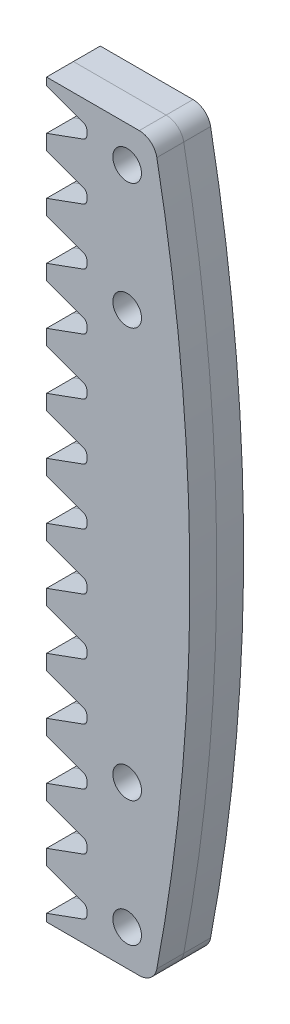
SolidWorks part; units mm, degrees
material "碳纤维"
ref_plane "前视基准面" through (0, 0, 0) normal (0, 0, 1) x (1, 0, 0)
ref_plane "上视基准面" through (0, 0, 0) normal (0, 1, 0) x (1, 0, 0)
ref_plane "右视基准面" through (0, 0, 0) normal (1, 0, 0) x (0, 0, -1)
ref_axis "基准轴1" through (0, -55, 0) along (0, 1, 0)
sketch "SketchCI.m_strSketchName" plane through (0, 0, 0) normal (0, 0, 1) x (1, 0, 0)
  line L0 (-2, 3.1416) -> (-2, -78.5398)
  line L1 (-2, -78.5398) -> (10, -78.5398)
  line L2 (10, -78.5398) -> (10, 3.1416)
  line L3 (10, 3.1416) -> (-2, 3.1416)
  dimension "D1" = 10
  dimension "D2" = 2
  dimension "D3" = 3.1416
  dimension "D4" = 81.6814
extrude "拉伸CI" add sketch "SketchCI.m_strSketchName" along normal mid plane 3
sketch "齿草图大直齿轮" plane through (0, 0, 0) normal (0, 0, 1) x (1, 0, 0)
  line L0 (-2.8229, 2.5983) -> (-2.8229, -2.5983)
  line L1 (-2.8229, -2.5983) -> (2.1052, -0.8046)
  line L2 (2.5, -0.2407) -> (2.5, 0.2407)
  line L3 (2.1052, 0.8046) -> (-2.8229, 2.5983)
  arc A0 (2.1052, -0.8046) -> (2.5, -0.2407) centre (1.9, -0.2407) ccw
  arc A1 (2.5, 0.2407) -> (2.1052, 0.8046) centre (1.9, 0.2407) ccw
  dimension "D1" = 1.2
  dimension "D2" = 1.2
  dimension "FLANKONEANGLE" = 70
  dimension "FLANKTWOANGLE" = 70
extrude "齿拉伸切除大直齿轮" cut sketch "齿草图大直齿轮" against normal through all both and the other way through all
pattern_linear "齿形大直齿轮" count 13 spacing 6.2832 along (0, -1, 0) of "齿拉伸切除大直齿轮"
sketch "辅助草图大直齿轮" plane through (0, 0, 0) normal (0, 0, 1) x (1, 0, 0)
  line L0 (0, 0) -> (0, -81.6814) construction
sketch "草图2" plane through (0, 0, 1.5) normal (0, 0, 1) x (1, 0, 0)
  line L0 (-2, -78.5398) -> (10, -78.5398) construction
  line L1 (10, 3.1416) -> (-2, 3.1416)
  line L2 (10, 3.1416) -> (10, -78.5398)
  line L3 (10, -78.5398) -> (-2, -78.5398)
  line L4 (-2, 3.1416) -> (-2, -78.5398)
  dimension "D1" = 12
sketch "草图7" plane through (0, 0, -1.5) normal (0, 0, -1) x (-1, 0, 0)
  line L1 (-2.5, -37.6991) -> (-10, -37.6991) construction
  line L3 (-2.5, -37.9399) -> (-2.5, -37.4584) construction
  line L5 (-7, -14.8584) -> (-7, -0.8584) construction
  line L6 (-10, -78.5398) -> (-10, 3.1416) construction
  line L7 (-10, 3.1416) -> (2, 3.1416) construction
  circle A1 centre (-7, -14.8584) radius 1.6
  circle A2 centre (-7, -0.8584) radius 1.6
  circle A5 centre (-7, -74.5398) radius 1.6
  circle A6 centre (-7, -60.5398) radius 1.6
  dimension "D1" = 3.2
  dimension "D2" = 4
  dimension "D3" = 3
  dimension "D4" = 14
extrude "切除-拉伸3" cut sketch "草图7" against normal through all
sketch "草图8" plane through (0, 0, -1.5) normal (0, 0, -1) x (-1, 0, 0)
  line L0 (-10, -37.6991) -> (196.4954, -37.6991) construction
  line L1 (-10, -78.5398) -> (-10, 3.1416) construction
  line L2 (-10, -37.6991) -> (-14, -37.6991) construction
  line L3 (-10, -78.5398) -> (-10, 3.1416)
  arc A0 (-10, 3.1416) -> (-10, -78.5398) centre (196.4954, -37.6991) ccw
  dimension "D1" = 4
extrude "凸台-拉伸1" add sketch "草图8" against normal up to surface (3 mm away) up to face at (5.4, -0.8584, 1.5)
fillet "圆角1" radius 2 2 edges at (10, 3.1416, 0) (10, -78.5398, 0)
sketch "草图9" plane through (0, 0, 1.5) normal (0, 0, 1) x (1, 0, 0)
  line L55 (8.3502, 3.1416) -> (-2, 3.1416)
  line L56 (-2, 3.1416) -> (-2, 2.2987)
  line L57 (-2, 2.2987) -> (2.1052, 0.8046)
  line L58 (2.5, 0.2407) -> (2.5, -0.2407)
  line L59 (2.1052, -0.8046) -> (-2, -2.2987)
  line L60 (-2, -2.2987) -> (-2, -3.9844)
  line L61 (-2, -3.9844) -> (2.1052, -5.4786)
  line L62 (2.5, -6.0424) -> (2.5, -6.5239)
  line L63 (2.1052, -7.0877) -> (-2, -8.5819)
  line L64 (-2, -8.5819) -> (-2, -10.2676)
  line L65 (-2, -10.2676) -> (2.1052, -11.7618)
  line L66 (2.5, -12.3256) -> (2.5, -12.8071)
  line L67 (2.1052, -13.3709) -> (-2, -14.8651)
  line L68 (-2, -14.8651) -> (-2, -16.5508)
  line L69 (-2, -16.5508) -> (2.1052, -18.045)
  line L70 (2.5, -18.6088) -> (2.5, -19.0903)
  line L71 (2.1052, -19.6541) -> (-2, -21.1483)
  line L72 (-2, -21.1483) -> (-2, -22.834)
  line L73 (-2, -22.834) -> (2.1052, -24.3282)
  line L74 (2.5, -24.892) -> (2.5, -25.3735)
  line L75 (2.1052, -25.9373) -> (-2, -27.4315)
  line L76 (-2, -27.4315) -> (-2, -29.1172)
  line L77 (-2, -29.1172) -> (2.1052, -30.6114)
  line L78 (2.5, -31.1752) -> (2.5, -31.6567)
  line L79 (2.1052, -32.2205) -> (-2, -33.7147)
  line L80 (-2, -33.7147) -> (-2, -35.4004)
  line L81 (-2, -35.4004) -> (2.1052, -36.8946)
  line L82 (2.5, -37.4584) -> (2.5, -37.9399)
  line L83 (2.1052, -38.5037) -> (-2, -39.9978)
  line L84 (-2, -39.9978) -> (-2, -41.6836)
  line L85 (-2, -41.6836) -> (2.1052, -43.1777)
  line L86 (2.5, -43.7416) -> (2.5, -44.223)
  line L87 (2.1052, -44.7869) -> (-2, -46.281)
  line L88 (-2, -46.281) -> (-2, -47.9667)
  line L89 (-2, -47.9667) -> (2.1052, -49.4609)
  line L90 (2.5, -50.0247) -> (2.5, -50.5062)
  line L91 (2.1052, -51.07) -> (-2, -52.5642)
  line L92 (-2, -52.5642) -> (-2, -54.2499)
  line L93 (-2, -54.2499) -> (2.1052, -55.7441)
  line L94 (2.5, -56.3079) -> (2.5, -56.7894)
  line L95 (2.1052, -57.3532) -> (-2, -58.8474)
  line L96 (-2, -58.8474) -> (-2, -60.5331)
  line L97 (-2, -60.5331) -> (2.1052, -62.0273)
  line L98 (2.5, -62.5911) -> (2.5, -63.0726)
  line L99 (2.1052, -63.6364) -> (-2, -65.1306)
  line L100 (-2, -65.1306) -> (-2, -66.8163)
  line L101 (-2, -66.8163) -> (2.1052, -68.3105)
  line L102 (2.5, -68.8743) -> (2.5, -69.3558)
  line L103 (2.1052, -69.9196) -> (-2, -71.4138)
  line L104 (-2, -71.4138) -> (-2, -73.0995)
  line L105 (-2, -73.0995) -> (2.1052, -74.5937)
  line L106 (2.5, -75.1575) -> (2.5, -75.639)
  line L107 (2.1052, -76.2028) -> (-2, -77.697)
  line L108 (-2, -77.697) -> (-2, -78.5398)
  line L109 (-2, -78.5398) -> (8.3502, -78.5398)
  line L110 (8.3502, 3.1416) -> (-2, 3.1416)
  line L111 (-2, 3.1416) -> (-2, 2.2987)
  line L112 (-2, 2.2987) -> (2.1052, 0.8046)
  line L113 (2.5, 0.2407) -> (2.5, -0.2407)
  line L114 (2.1052, -0.8046) -> (-2, -2.2987)
  line L115 (-2, -2.2987) -> (-2, -3.9844)
  line L116 (-2, -3.9844) -> (2.1052, -5.4786)
  line L117 (2.5, -6.0424) -> (2.5, -6.5239)
  line L118 (2.1052, -7.0877) -> (-2, -8.5819)
  line L119 (-2, -8.5819) -> (-2, -10.2676)
  line L120 (-2, -10.2676) -> (2.1052, -11.7618)
  line L121 (2.5, -12.3256) -> (2.5, -12.8071)
  line L122 (2.1052, -13.3709) -> (-2, -14.8651)
  line L123 (-2, -14.8651) -> (-2, -16.5508)
  line L124 (-2, -16.5508) -> (2.1052, -18.045)
  line L125 (2.5, -18.6088) -> (2.5, -19.0903)
  line L126 (2.1052, -19.6541) -> (-2, -21.1483)
  line L127 (-2, -21.1483) -> (-2, -22.834)
  line L128 (-2, -22.834) -> (2.1052, -24.3282)
  line L129 (2.5, -24.892) -> (2.5, -25.3735)
  line L130 (2.1052, -25.9373) -> (-2, -27.4315)
  line L131 (-2, -27.4315) -> (-2, -29.1172)
  line L132 (-2, -29.1172) -> (2.1052, -30.6114)
  line L133 (2.5, -31.1752) -> (2.5, -31.6567)
  line L134 (2.1052, -32.2205) -> (-2, -33.7147)
  line L135 (-2, -33.7147) -> (-2, -35.4004)
  line L136 (-2, -35.4004) -> (2.1052, -36.8946)
  line L137 (2.5, -37.4584) -> (2.5, -37.9399)
  line L138 (2.1052, -38.5037) -> (-2, -39.9978)
  line L139 (-2, -39.9978) -> (-2, -41.6836)
  line L140 (-2, -41.6836) -> (2.1052, -43.1777)
  line L141 (2.5, -43.7416) -> (2.5, -44.223)
  line L142 (2.1052, -44.7869) -> (-2, -46.281)
  line L143 (-2, -46.281) -> (-2, -47.9667)
  line L144 (-2, -47.9667) -> (2.1052, -49.4609)
  line L145 (2.5, -50.0247) -> (2.5, -50.5062)
  line L146 (2.1052, -51.07) -> (-2, -52.5642)
  line L147 (-2, -52.5642) -> (-2, -54.2499)
  line L148 (-2, -54.2499) -> (2.1052, -55.7441)
  line L149 (2.5, -56.3079) -> (2.5, -56.7894)
  line L150 (2.1052, -57.3532) -> (-2, -58.8474)
  line L151 (-2, -58.8474) -> (-2, -60.5331)
  line L152 (-2, -60.5331) -> (2.1052, -62.0273)
  line L153 (2.5, -62.5911) -> (2.5, -63.0726)
  line L154 (2.1052, -63.6364) -> (-2, -65.1306)
  line L155 (-2, -65.1306) -> (-2, -66.8163)
  line L156 (-2, -66.8163) -> (2.1052, -68.3105)
  line L157 (2.5, -68.8743) -> (2.5, -69.3558)
  line L158 (2.1052, -69.9196) -> (-2, -71.4138)
  line L159 (-2, -71.4138) -> (-2, -73.0995)
  line L160 (-2, -73.0995) -> (2.1052, -74.5937)
  line L161 (2.5, -75.1575) -> (2.5, -75.639)
  line L162 (2.1052, -76.2028) -> (-2, -77.697)
  line L163 (-2, -77.697) -> (-2, -78.5398)
  line L164 (-2, -78.5398) -> (8.3502, -78.5398)
  circle A0 centre (7, -0.8584) radius 1.6 construction
  circle A1 centre (7, -14.8584) radius 1.6 construction
  circle A2 centre (7, -60.5398) radius 1.6 construction
  circle A3 centre (7, -74.5398) radius 1.6 construction
  circle A4 centre (7, -0.8584) radius 1.6
  circle A5 centre (7, -14.8584) radius 1.6
  circle A6 centre (7, -60.5398) radius 1.6
  circle A7 centre (7, -74.5398) radius 1.6
  arc A29 (10.3152, -76.9124) -> (10.3152, 1.5142) centre (-196.4954, -37.6991) ccw
  arc A30 (10.3152, 1.5142) -> (8.3502, 3.1416) centre (8.3502, 1.1416) ccw
  arc A31 (2.5, 0.2407) -> (2.1052, 0.8046) centre (1.9, 0.2407) ccw
  arc A32 (2.1052, -0.8046) -> (2.5, -0.2407) centre (1.9, -0.2407) ccw
  arc A33 (2.5, -6.0424) -> (2.1052, -5.4786) centre (1.9, -6.0424) ccw
  arc A34 (2.1052, -7.0877) -> (2.5, -6.5239) centre (1.9, -6.5239) ccw
  arc A35 (2.5, -12.3256) -> (2.1052, -11.7618) centre (1.9, -12.3256) ccw
  arc A36 (2.1052, -13.3709) -> (2.5, -12.8071) centre (1.9, -12.8071) ccw
  arc A37 (2.5, -18.6088) -> (2.1052, -18.045) centre (1.9, -18.6088) ccw
  arc A38 (2.1052, -19.6541) -> (2.5, -19.0903) centre (1.9, -19.0903) ccw
  arc A39 (2.5, -24.892) -> (2.1052, -24.3282) centre (1.9, -24.892) ccw
  arc A40 (2.1052, -25.9373) -> (2.5, -25.3735) centre (1.9, -25.3735) ccw
  arc A41 (2.5, -31.1752) -> (2.1052, -30.6114) centre (1.9, -31.1752) ccw
  arc A42 (2.1052, -32.2205) -> (2.5, -31.6567) centre (1.9, -31.6567) ccw
  arc A43 (2.5, -37.4584) -> (2.1052, -36.8946) centre (1.9, -37.4584) ccw
  arc A44 (2.1052, -38.5037) -> (2.5, -37.9399) centre (1.9, -37.9399) ccw
  arc A45 (2.5, -43.7416) -> (2.1052, -43.1777) centre (1.9, -43.7416) ccw
  arc A46 (2.1052, -44.7869) -> (2.5, -44.223) centre (1.9, -44.223) ccw
  arc A47 (2.5, -50.0247) -> (2.1052, -49.4609) centre (1.9, -50.0247) ccw
  arc A48 (2.1052, -51.07) -> (2.5, -50.5062) centre (1.9, -50.5062) ccw
  arc A49 (2.5, -56.3079) -> (2.1052, -55.7441) centre (1.9, -56.3079) ccw
  arc A50 (2.1052, -57.3532) -> (2.5, -56.7894) centre (1.9, -56.7894) ccw
  arc A51 (2.5, -62.5911) -> (2.1052, -62.0273) centre (1.9, -62.5911) ccw
  arc A52 (2.1052, -63.6364) -> (2.5, -63.0726) centre (1.9, -63.0726) ccw
  arc A53 (2.5, -68.8743) -> (2.1052, -68.3105) centre (1.9, -68.8743) ccw
  arc A54 (2.1052, -69.9196) -> (2.5, -69.3558) centre (1.9, -69.3558) ccw
  arc A55 (2.5, -75.1575) -> (2.1052, -74.5937) centre (1.9, -75.1575) ccw
  arc A56 (2.1052, -76.2028) -> (2.5, -75.639) centre (1.9, -75.639) ccw
  arc A57 (8.3502, -78.5398) -> (10.3152, -76.9124) centre (8.3502, -76.5398) ccw
  arc A58 (10.3152, -76.9124) -> (10.3152, 1.5142) centre (-196.4954, -37.6991) ccw
  arc A59 (10.3152, 1.5142) -> (8.3502, 3.1416) centre (8.3502, 1.1416) ccw
  arc A60 (2.5, 0.2407) -> (2.1052, 0.8046) centre (1.9, 0.2407) ccw
  arc A61 (2.1052, -0.8046) -> (2.5, -0.2407) centre (1.9, -0.2407) ccw
  arc A62 (2.5, -6.0424) -> (2.1052, -5.4786) centre (1.9, -6.0424) ccw
  arc A63 (2.1052, -7.0877) -> (2.5, -6.5239) centre (1.9, -6.5239) ccw
  arc A64 (2.5, -12.3256) -> (2.1052, -11.7618) centre (1.9, -12.3256) ccw
  arc A65 (2.1052, -13.3709) -> (2.5, -12.8071) centre (1.9, -12.8071) ccw
  arc A66 (2.5, -18.6088) -> (2.1052, -18.045) centre (1.9, -18.6088) ccw
  arc A67 (2.1052, -19.6541) -> (2.5, -19.0903) centre (1.9, -19.0903) ccw
  arc A68 (2.5, -24.892) -> (2.1052, -24.3282) centre (1.9, -24.892) ccw
  arc A69 (2.1052, -25.9373) -> (2.5, -25.3735) centre (1.9, -25.3735) ccw
  arc A70 (2.5, -31.1752) -> (2.1052, -30.6114) centre (1.9, -31.1752) ccw
  arc A71 (2.1052, -32.2205) -> (2.5, -31.6567) centre (1.9, -31.6567) ccw
  arc A72 (2.5, -37.4584) -> (2.1052, -36.8946) centre (1.9, -37.4584) ccw
  arc A73 (2.1052, -38.5037) -> (2.5, -37.9399) centre (1.9, -37.9399) ccw
  arc A74 (2.5, -43.7416) -> (2.1052, -43.1777) centre (1.9, -43.7416) ccw
  arc A75 (2.1052, -44.7869) -> (2.5, -44.223) centre (1.9, -44.223) ccw
  arc A76 (2.5, -50.0247) -> (2.1052, -49.4609) centre (1.9, -50.0247) ccw
  arc A77 (2.1052, -51.07) -> (2.5, -50.5062) centre (1.9, -50.5062) ccw
  arc A78 (2.5, -56.3079) -> (2.1052, -55.7441) centre (1.9, -56.3079) ccw
  arc A79 (2.1052, -57.3532) -> (2.5, -56.7894) centre (1.9, -56.7894) ccw
  arc A80 (2.5, -62.5911) -> (2.1052, -62.0273) centre (1.9, -62.5911) ccw
  arc A81 (2.1052, -63.6364) -> (2.5, -63.0726) centre (1.9, -63.0726) ccw
  arc A82 (2.5, -68.8743) -> (2.1052, -68.3105) centre (1.9, -68.8743) ccw
  arc A83 (2.1052, -69.9196) -> (2.5, -69.3558) centre (1.9, -69.3558) ccw
  arc A84 (2.5, -75.1575) -> (2.1052, -74.5937) centre (1.9, -75.1575) ccw
  arc A85 (2.1052, -76.2028) -> (2.5, -75.639) centre (1.9, -75.639) ccw
  arc A86 (8.3502, -78.5398) -> (10.3152, -76.9124) centre (8.3502, -76.5398) ccw
  dimension "D1" = 0
extrude "凸台-拉伸2" add sketch "草图9" along normal blind 3 separate body
